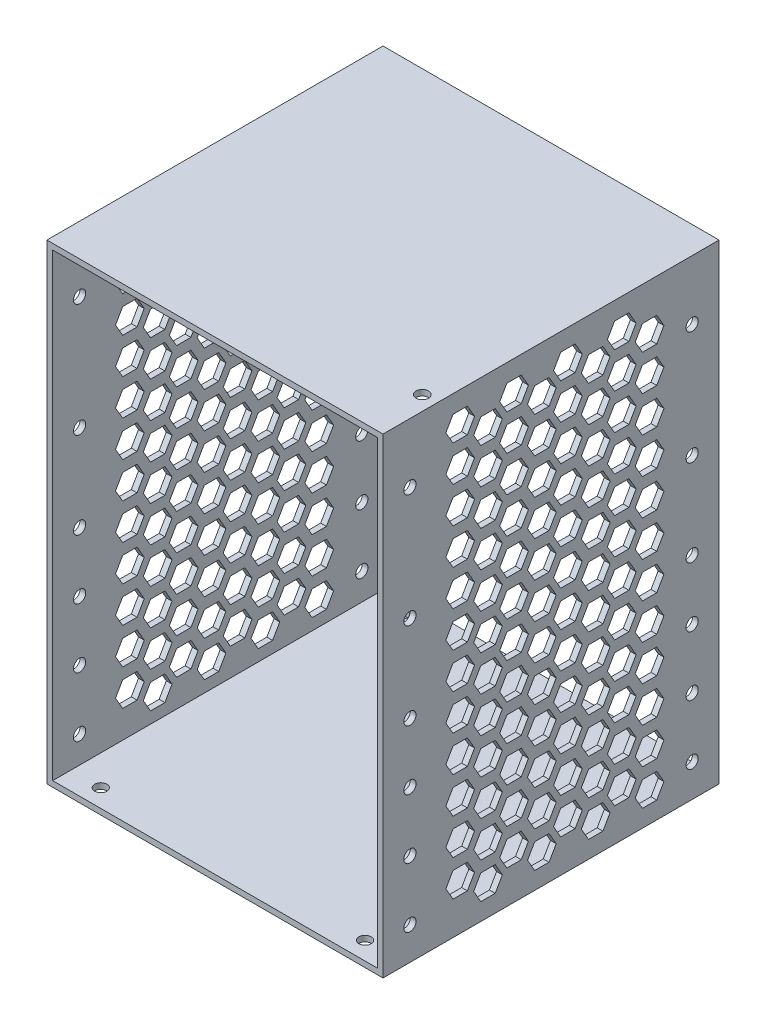
SolidWorks part; units mm, degrees
ref_plane "Front Plane" through (0, 0, 0) normal (0, 0, 1) x (1, 0, 0)
ref_plane "Top Plane" through (0, 0, 0) normal (0, 1, 0) x (1, 0, 0)
ref_plane "Right Plane" through (0, 0, 0) normal (1, 0, 0) x (0, 0, -1)
sketch "Sketch1" plane through (0, 0, 0) normal (0, 0, 1) x (1, 0, 0)
  line L0 (-45.2, 26.84) -> (45.2, 26.84)
  line L1 (45.2, 26.84) -> (45.2, -101.16)
  line L2 (45.2, -101.16) -> (-45.2, -101.16)
  line L3 (-45.2, -101.16) -> (-45.2, 26.84)
  line L5 (-46.8, 28.44) -> (46.8, 28.44)
  line L6 (-46.8, 28.44) -> (-46.8, -102.76)
  line L7 (-46.8, -102.76) -> (46.8, -102.76)
  line L8 (46.8, 28.44) -> (46.8, -102.76)
  dimension "D1" = 90.4
  dimension "D2" = 128
  dimension "D3" = 1.6
  dimension "D4" = 1.6
  dimension "D5" = 1.6
  dimension "D6" = 1.6
  dimension "D7" = 45.2
  dimension "D8" = 45.2
extrude "Boss-Extrude1" add sketch "Sketch1" along normal blind 93.6
sketch "Sketch2" plane through (46.8, 0, 0) normal (1, 0, 0) x (0, 0, -1)
  line L0 (-93.6, 28.44) -> (-93.6, -102.76)
  line L1 (-93.6, 28.44) -> (0, 28.44) construction
  line L2 (-93.6, -102.76) -> (-93.6, 28.44) construction
  line L3 (-93.6, -102.76) -> (0, -102.76) construction
  line L4 (-93.6, -85.36) -> (0, -85.36) construction
  line L5 (0, -102.76) -> (0, 28.44) construction
  line L6 (-93.6, -68.76) -> (0, -68.76) construction
  line L7 (-93.6, -52.16) -> (0, -52.16) construction
  line L8 (-93.6, -35.56) -> (0, -35.56) construction
  line L9 (-93.6, -3.96) -> (0, -3.96) construction
  line L10 (-93.6, -43.86) -> (0, -43.86)
  line L11 (-93.6, -60.46) -> (0, -60.46)
  line L12 (-93.6, -77.06) -> (0, -77.06)
  line L13 (-93.6, -93.66) -> (0, -93.66)
  line L14 (-93.6, -19.76) -> (0, -19.76)
  line L15 (-93.6, 11.84) -> (0, 11.84)
  line L16 (-93.6, -12.26) -> (0, -12.26)
  line L17 (-93.6, -84.56) -> (0, -84.56)
  line L18 (0, -84.56) -> (0, -86.16)
  line L19 (0, -86.16) -> (-93.6, -86.16)
  line L20 (-93.6, -67.96) -> (0, -67.96)
  line L21 (0, -67.96) -> (0, -69.56)
  line L22 (0, -69.56) -> (-93.6, -69.56)
  line L23 (-93.6, -51.36) -> (0, -51.36)
  line L24 (0, -51.36) -> (0, -52.96)
  line L25 (0, -52.96) -> (-93.6, -52.96)
  line L26 (-93.6, -34.76) -> (0, -34.76)
  line L27 (-93.6, -36.36) -> (0, -36.36)
  line L29 (-93.6, -3.16) -> (0, -3.16)
  line L30 (0, -3.16) -> (0, -4.76)
  line L31 (0, -4.76) -> (-93.6, -4.76)
  circle A11 centre (-86.1, 11.84) radius 0.75
  circle A13 centre (-86.1, -19.76) radius 0.75
  circle A14 centre (-86.1, -43.86) radius 0.75
  circle A15 centre (-86.1, -60.46) radius 0.75
  circle A16 centre (-86.1, -77.06) radius 0.75
  circle A17 centre (-86.1, -93.66) radius 0.75
  circle A18 centre (-7.5, 11.84) radius 0.75
  circle A20 centre (-7.5, -19.76) radius 0.75
  circle A21 centre (-7.5, -43.86) radius 0.75
  circle A22 centre (-7.5, -60.46) radius 0.75
  circle A23 centre (-7.5, -77.06) radius 0.75
  circle A24 centre (-7.5, -93.66) radius 0.75
  circle A25 centre (-84, -12.26) radius 0.75
  circle A26 centre (-10, -12.26) radius 0.75
  point P82 (0, 0)
  point P83 (0, 0)
  point P84 (0, 0)
  dimension "D7" = 16.6
  dimension "D8" = 15.8
  dimension "D9" = 8.3
  dimension "D10" = 8.3
  dimension "D11" = 8.3
  dimension "D12" = 8.3
  dimension "D13" = 1.5
  dimension "D14" = 7.5
  dimension "D15" = 7.5
  dimension "D16" = 1.5
  dimension "D17" = 1.5
  dimension "D18" = 1.5
  dimension "D19" = 1.5
  dimension "D20" = 1.5
  dimension "D21" = 1.5
  dimension "D22" = 1.5
  dimension "D23" = 1.5
  dimension "D24" = 1.5
  dimension "D25" = 1.5
  dimension "D26" = 1.5
  dimension "D1" = 17.4
  dimension "D2" = 16.6
  dimension "D3" = 16.6
  dimension "D4" = 16.6
  dimension "D5" = 31.6
  dimension "D6" = 32.4
  dimension "D27" = 8.3
  dimension "D28" = 0.8
  dimension "D29" = 0.8
  dimension "D30" = 0.8
  dimension "D31" = 0.8
  dimension "D32" = 0.8
  dimension "D33" = 0.8
  dimension "D34" = 0.8
  dimension "D35" = 0.8
  dimension "D36" = 0.8
  dimension "D37" = 0.8
  dimension "D38" = 15
extrude "Cut-Extrude1" cut sketch "Sketch2" against normal blind 100 contours L15 A11 | L15 A11 | L15 A18 | L15 A18 | L14 A13 | L14 A13 | L10 A21 | L10 A14 | L11 A15 | L11 A22 | L11 A22 | L12 A16 | L12 A16 | L12 A23 | L13 A17 | L13 A17 | L12 A23 | L13 A24 | L13 A24 | A20 | A21 | A14 | A15 region at (46.8, -19.4417, 86.1) region at (46.8, -20.0783, 86.1) region at (46.8, -44.1783, 7.5) region at (46.8, -43.5417, 86.1) region at (46.8, -60.1417, 7.5) region at (46.8, -60.7783, 7.5) region at (46.8, -60.1417, 86.1) region at (46.8, -76.7417, 7.5) region at (46.8, -77.3783, 7.5) region at (46.8, -76.7417, 86.1) region at (46.8, -77.3783, 86.1) region at (46.8, -93.3417, 7.5) region at (46.8, -93.9783, 7.5) region at (46.8, -93.3417, 86.1) region at (46.8, -93.9783, 86.1) region at (46.8, 12.1583, 7.5) region at (46.8, 11.5217, 7.5) region at (46.8, 12.1583, 86.1) region at (46.8, 11.5217, 86.1)
sketch "Sketch6" plane through (46.8, 0, 0) normal (1, 0, 0) x (0, 0, -1)
  line L0 (-76.1, 19.9759) -> (-74.1, 23.44)
  line L1 (-74.1, 23.44) -> (-70.1, 23.44)
  line L2 (-70.1, 23.44) -> (-68.1, 19.9759)
  line L3 (-68.1, 19.9759) -> (-70.1, 16.5118)
  line L4 (-70.1, 16.5118) -> (-74.1, 16.5118)
  line L5 (-74.1, 16.5118) -> (-76.1, 19.9759)
  line L18 (-93.6, 28.44) -> (0, 28.44) construction
  line L19 (-93.6, -102.76) -> (-93.6, 28.44) construction
  line L20 (-68.3557, 15.5047) -> (-66.3557, 18.9688)
  line L21 (-66.3557, 18.9688) -> (-62.3557, 18.9688)
  line L22 (-62.3557, 18.9688) -> (-60.3557, 15.5047)
  line L23 (-60.3557, 15.5047) -> (-62.3557, 12.0406)
  line L24 (-62.3557, 12.0406) -> (-66.3557, 12.0406)
  line L25 (-66.3557, 12.0406) -> (-68.3557, 15.5047)
  dimension "D1" = 120
  dimension "D2" = 120
  dimension "D3" = 120
  dimension "D4" = 4
  dimension "D5" = 4
  dimension "D6" = 4
  dimension "D7" = 4
  dimension "D8" = 5
  dimension "D9" = 17.5
  dimension "D10" = 120
  dimension "D11" = 120
  dimension "D12" = 120
  dimension "D13" = 4
  dimension "D14" = 4
  dimension "D15" = 4
  dimension "D16" = 4
  dimension "D17" = 2.0142
  dimension "D18" = 2.0142
  dimension "D19" = 25.2443
extrude "Cut-Extrude4" cut sketch "Sketch6" against normal blind 100
pattern_linear "LPattern2" count 4 spacing 15 along (0, 0, -1) count 12 spacing 10 along (0, -1, 0) of "Cut-Extrude4"
hole_wizard "M3 Clearance Hole1" positions "Sketch7" profile "Sketch8" hole size "M3" standard "ANSI Metric" end condition through all
sketch "Sketch7" plane through (-46.8, 0, 0) normal (-1, 0, 0) x (0, 0, 1)
  point P0 (7.5, 11.84)
  point P3 (86.1, 11.84)
  point P6 (7.5, -19.76)
  point P9 (7.5, -43.86)
  point P12 (86.1, -19.76)
  point P15 (86.1, -43.86)
  point P18 (86.1, -60.46)
  point P21 (86.1, -77.06)
  point P26 (7.5, -93.66)
  point P29 (7.5, -77.06)
  point P32 (7.5, -60.46)
  point P40 (86.1, -93.66)
sketch "Sketch8" plane through (-46.8, 11.84, 7.5) normal (0, 1, 0) x (0, 0, 1)
  line L0 (0, 0) -> (0, 93.6)
  line L1 (0, 93.6) -> (1.7, 93.6)
  line L2 (1.7, 93.6) -> (1.7, 0)
  line L5 (1.7, 0) -> (0, 0)
  line L11 (0, -6.35) -> (0, 107.95) construction
  dimension "Thru Hole Dia." = 3.4
  dimension "Thru Hole Depth" = 93.6
sketch "Sketch9" plane through (0, 0, 0) normal (0, 0, 1) x (1, 0, 0)
  line L1 (-30, -108.3026) -> (30, -108.3026)
  line L2 (-30, -108.3026) -> (-30, -39.5314)
  line L3 (-30, -39.5314) -> (30, -39.5314)
  line L4 (30, -108.3026) -> (30, -39.5314)
  dimension "D1" = 30
  dimension "D2" = 30
sketch "Sketch10" plane through (0, -102.76, 0) normal (0, -1, 0) x (1, 0, 0)
  line L0 (45.2, 93.6) -> (-45.2, 93.6) construction
  line L3 (-46.8, 0) -> (46.8, 0) construction
  line L5 (-46.8, 0) -> (46.8, 0) construction
  line L6 (-46.8, 93.6) -> (46.8, 93.6) construction
  line L7 (-46.8, 93.6) -> (-46.8, 0) construction
  line L8 (46.8, 93.6) -> (46.8, 0) construction
  circle A0 centre (-36.8, 88.6) radius 2.9453
  circle A1 centre (-36.8, 5) radius 1.9301
  circle A2 centre (36.8, 5) radius 1.9498
  circle A3 centre (36.8, 88.6) radius 2.427
  dimension "D1" = 5
  dimension "D2" = 10
  dimension "D3" = 10
  dimension "D4" = 5
  dimension "D5" = 10
  dimension "D6" = 5
  dimension "D7" = 5
  dimension "D8" = 10
hole_wizard "M3 Clearance Hole2" positions "Sketch11" profile "Sketch12" hole size "M3" standard "ANSI Metric" end condition up to next
sketch "Sketch11" plane through (0, -102.76, 0) normal (0, -1, 0) x (-1, 0, 0)
  point P0 (-36.8, -5)
  point P3 (-36.8, -88.6)
  point P6 (36.8, -88.6)
  point P9 (36.8, -5)
sketch "Sketch12" plane through (36.8, -102.76, 5) normal (1, 0, 0) x (0, 0, -1)
  line L0 (0, 0) -> (0, 1.6)
  line L1 (0, 1.6) -> (1.7, 1.6)
  line L2 (1.7, 1.6) -> (1.7, 0)
  line L5 (1.7, 0) -> (0, 0)
  line L11 (0, -6.35) -> (0, 107.95) construction
  dimension "Thru Hole Dia." = 3.4
  dimension "Thru Hole Depth" = 1.6
sketch "Sketch16" plane through (0, 28.44, 0) normal (0, 1, 0) x (1, 0, 0)
  line L0 (46.8, -93.6) -> (46.8, 0) construction
  line L1 (46.8, -93.6) -> (-46.8, -93.6) construction
  circle A0 centre (42.75, -78.6) radius 1.75
  dimension "D1" = 3.5
  dimension "D2" = 4.05
  dimension "D3" = 15
extrude "Cut-Extrude6" cut sketch "Sketch16" against normal blind 141
